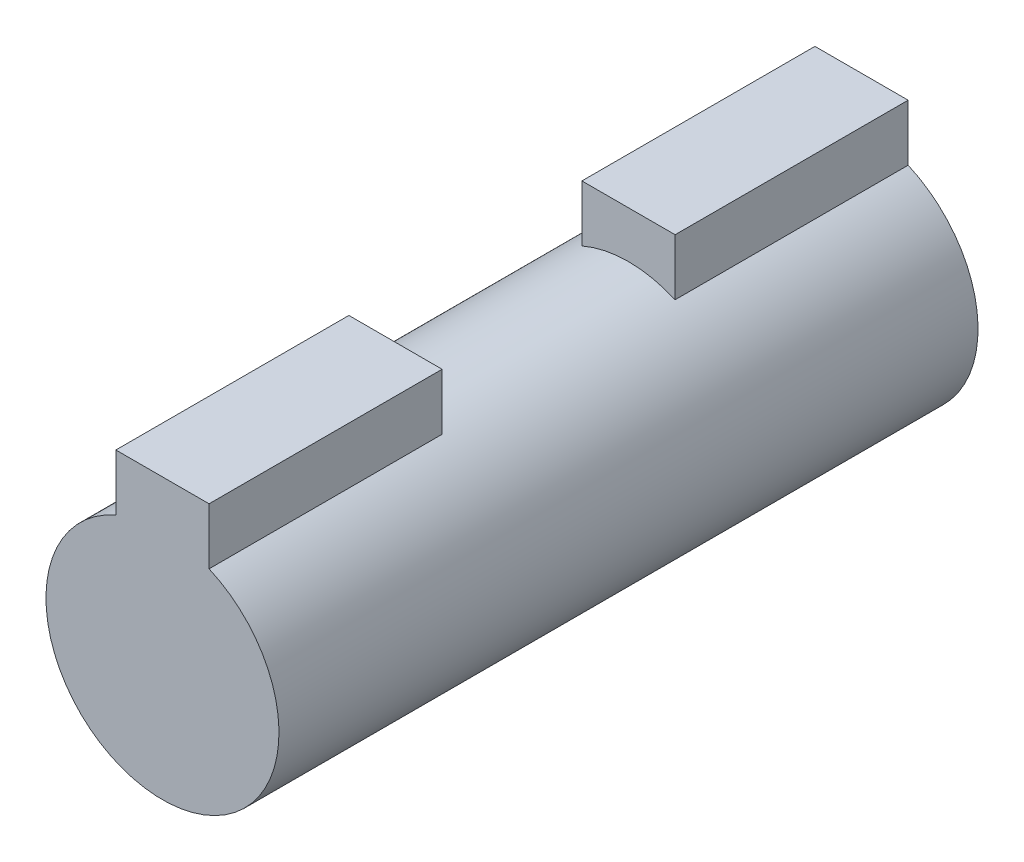
SolidWorks part; units mm, degrees
ref_plane "Front Plane" through (0, 0, 0) normal (0, 0, 1) x (1, 0, 0)
ref_plane "Top Plane" through (0, 0, 0) normal (0, 1, 0) x (1, 0, 0)
ref_plane "Right Plane" through (0, 0, 0) normal (1, 0, 0) x (0, 0, -1)
sketch "Sketch1" plane through (0, 0, 0) normal (0, 0, 1) x (1, 0, 0)
  line L1 (2, 7) -> (-2, 7)
  line L2 (2, 7) -> (2, 3)
  line L3 (2, 3) -> (-2, 3)
  line L4 (-2, 7) -> (-2, 3)
  line L5 (2, 7) -> (-2, 3) construction
  line L6 (2, 3) -> (-2, 7) construction
  circle A0 centre (0, 0) radius 5
  point P3 (0, 5)
  dimension "D1" = 10
  dimension "D2" = 4
  dimension "D3" = 7
extrude "Boss-Extrude1" add sketch "Sketch1" along normal blind 30 contours A0 L2 L1 L4 | L2 A0 L4 L3 | L4 A0 L2 L3 region at (0, 5.9281, 0) region at (0, -0.4126, 0) region at (0, 3.9357, 0)
sketch "Sketch2" plane through (0, 0, 30) normal (0, 0, 1) x (1, 0, 0)
  circle A0 centre (0, 0) radius 5
  circle A1 centre (0, 0) radius 10
  dimension "D1" = 20
extrude "Cut-Extrude1" cut sketch "Sketch2" against normal blind 10 from offset 10 offset against normal yes
